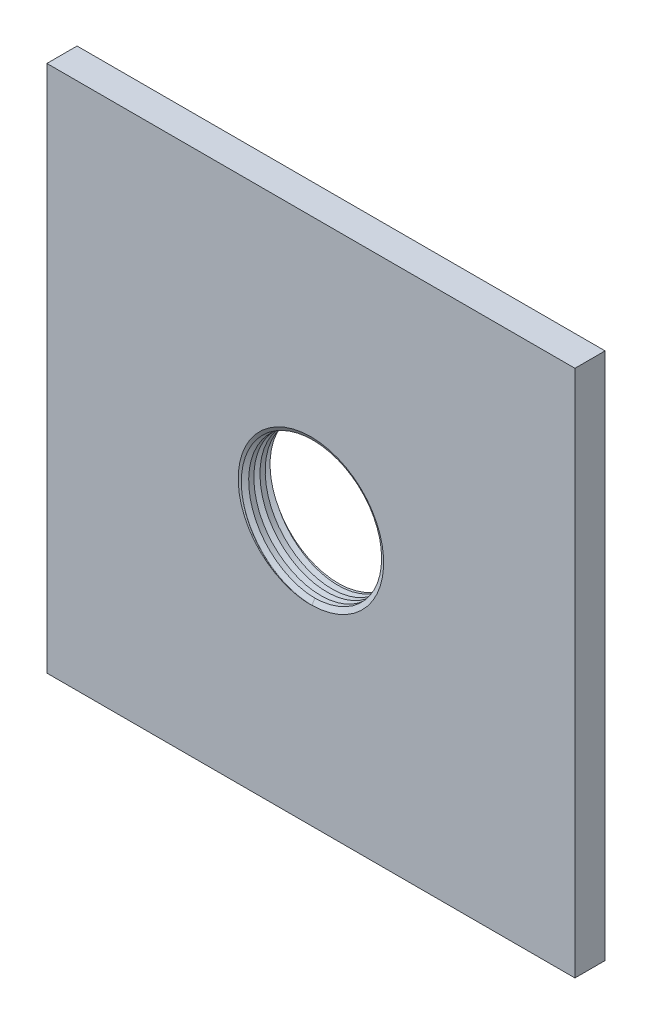
SolidWorks part; units mm, degrees
ref_plane "Front Plane" through (0, 0, 0) normal (0, 0, 1) x (1, 0, 0)
ref_plane "Top Plane" through (0, 0, 0) normal (0, 1, 0) x (1, 0, 0)
ref_plane "Right Plane" through (0, 0, 0) normal (1, 0, 0) x (0, 0, -1)
sketch "Sketch1" plane through (0, 0, 0) normal (0, 0, 1) x (1, 0, 0)
  line L1 (0, 0) -> (35, 0)
  line L2 (0, 0) -> (0, 35)
  line L3 (0, 35) -> (35, 35)
  line L4 (35, 0) -> (35, 35)
  dimension "D1" = 35
  dimension "D2" = 35
extrude "Boss-Extrude1" add sketch "Sketch1" along normal blind 2
sketch "Sketch2" plane through (0, 0, 2) normal (0, 0, 1) x (1, 0, 0)
  circle A0 centre (17.5, 17.5) radius 4.5
  dimension "D1" = 9
extrude "Cut-Extrude1" cut sketch "Sketch2" against normal up to next
sketch "Sketch21" plane through (0, 0, 2) normal (0, 0, 1) x (1, 0, 0)
  circle A0 centre (17.5, 17.5) radius 4.5 construction
  circle A1 centre (17.5, 17.5) radius 4.5
curve "Helix/Spiral8" pitch 0.75 height 2.25 radius 4.5 centre (17.5, 17.5, 2) axis (0, 0, -1) start towards (1, 0, 0)
ref_plane "Plane5" through (0, 17.5, 0) normal (0, -1, 0) x (-1, 0, 0)
sketch "Sketch22" plane through (0, 17.5, 0) normal (0, -1, 0) x (-1, 0, 0)
  line L0 (-35, -2) -> (-35, 0) construction
  line L1 (-22, -2.406) -> (-22, -2)
  line L2 (-22, -2) -> (-22.3216, -2.1857)
  line L3 (-22.3216, -2.2203) -> (-22, -2.406)
  circle A0 centre (-22.1172, -2.203) radius 0.1172 construction
  arc A1 (-22.3216, -2.2203) -> (-22.3216, -2.1857) centre (-22.3116, -2.203) cw
  dimension "D2" = 0.02
  dimension "D1" = 0.406
sweep "Cut-Sweep9" cut profiles "Sketch22" path "Helix/Spiral8"
sketch "Sketch24" plane through (0, 0, 2) normal (0, 0, 1) x (1, 0, 0)
  circle A0 centre (17.5, 17.5) radius 4.8216
extrude "Cut-Extrude2" cut sketch "Sketch24" against normal blind 10 draft 60
sketch "Sketch25" plane through (0, 0, 0) normal (0, 0, -1) x (-1, 0, 0)
  circle A0 centre (-17.5, 17.5) radius 4.8216
extrude "Cut-Extrude3" cut sketch "Sketch25" against normal blind 10 draft 60
